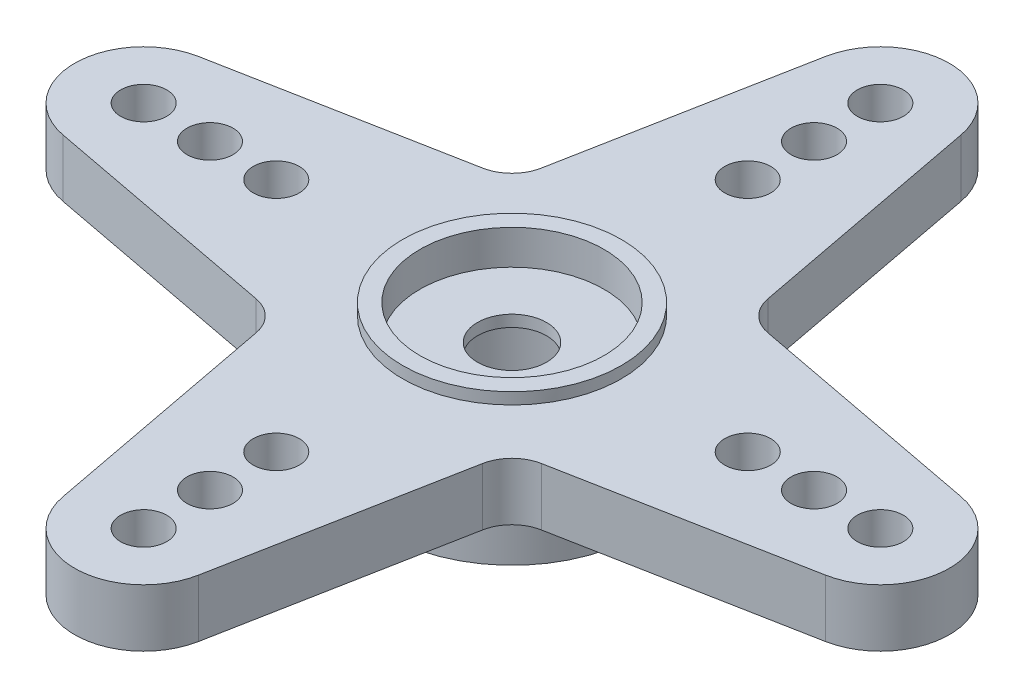
SolidWorks part; units mm, degrees
ref_plane "Front Plane" through (0, 0, 0) normal (0, 0, 1) x (1, 0, 0)
ref_plane "Top Plane" through (0, 0, 0) normal (0, 1, 0) x (1, 0, 0)
ref_plane "Right Plane" through (0, 0, 0) normal (1, 0, 0) x (0, 0, -1)
sketch "Sketch1" plane through (0, 0, 0) normal (0, 1, 0) x (1, 0, 0)
  line L0 (-1000, 0) -> (49000, 0) construction
  line L1 (0, -1000) -> (0, 49000) construction
  line L2 (-3.9044, 4.9148) -> (-2.3393, 13.1449)
  line L3 (3.9044, 4.9148) -> (2.3393, 13.1449)
  line L4 (4.9148, 3.9044) -> (13.1449, 2.3393)
  line L5 (4.9148, -3.9044) -> (13.1449, -2.3393)
  line L6 (3.9044, -4.9148) -> (2.3393, -13.1449)
  line L7 (-3.9044, -4.9148) -> (-2.3393, -13.1449)
  line L8 (-4.0659, 4.0659) -> (-4.0659, -4.0659) construction
  line L9 (-4.0659, 4.0659) -> (4.0659, 4.0659) construction
  line L10 (-4.0659, -4.0659) -> (4.0659, -4.0659) construction
  line L11 (4.0659, 4.0659) -> (4.0659, -4.0659) construction
  line L12 (-4.9148, -3.9044) -> (-13.1449, -2.3393)
  line L13 (-4.9148, 3.9044) -> (-13.1449, 2.3393)
  circle A0 centre (0, 0) radius 1.1906
  circle A1 centre (0, 0) radius 5.75 construction
  arc A2 (-2.3393, 13.1449) -> (2.3393, 13.1449) centre (0, 12.7) cw
  circle A3 centre (0, 12.7) radius 0.7937
  circle A4 centre (0, 10.414) radius 0.7937
  circle A5 centre (0, 8.128) radius 0.7937
  arc A6 (13.1449, 2.3393) -> (13.1449, -2.3393) centre (12.7, 0) cw
  circle A7 centre (12.7, 0) radius 0.7937
  circle A8 centre (10.414, 0) radius 0.7937
  circle A9 centre (8.128, 0) radius 0.7937
  arc A10 (2.3393, -13.1449) -> (-2.3393, -13.1449) centre (0, -12.7) cw
  circle A11 centre (0, -12.7) radius 0.7937
  circle A12 centre (0, -10.414) radius 0.7937
  circle A13 centre (0, -8.128) radius 0.7938
  arc A14 (-13.1449, -2.3393) -> (-13.1449, 2.3393) centre (-12.7, 0) cw
  circle A15 centre (-12.7, 0) radius 0.7937
  circle A16 centre (-10.414, 0) radius 0.7937
  circle A17 centre (-8.128, 0) radius 0.7937
  arc A18 (3.9044, 4.9148) -> (4.9148, 3.9044) centre (5.1521, 5.1521) ccw
  arc A19 (-3.9044, -4.9148) -> (-4.9148, -3.9044) centre (-5.1521, -5.1521) ccw
  arc A20 (-3.9044, 4.9148) -> (-4.9148, 3.9044) centre (-5.1521, 5.1521) cw
  arc A21 (3.9044, -4.9148) -> (4.9148, -3.9044) centre (5.1521, -5.1521) cw
  point P56 (4.0659, 0)
  point P57 (-4.0659, 0)
  dimension "D1" = 11.5
  dimension "D2" = 2.3813
  dimension "D3" = 2.3813
  dimension "D5" = 1.5875
  dimension "D8" = 1.27
  dimension "D9" = 1.27
  dimension "D10" = 1.27
  dimension "D11" = 1.27
  dimension "D4" = 12.7
  dimension "D6" = 3
  dimension "D7" = 4
extrude "Boss-Extrude1" add sketch "Sketch1" along normal blind 1.9844
sketch "Sketch2" plane through (0, 1.9844, 0) normal (0, 1, 0) x (1, 0, 0)
  circle A0 centre (0, 0) radius 3.175
  dimension "D1" = 6.35
extrude "Cut-Extrude1" cut sketch "Sketch2" against normal blind 0.7937
sketch "Sketch3" plane through (0, 0, 0) normal (0, -1, 0) x (1, 0, 0)
  circle A0 centre (0, 0) radius 4.3656
  dimension "D1" = 8.7312
extrude "Boss-Extrude2" add sketch "Sketch3" along normal blind 2.3813
sketch "Sketch4" plane through (0, -2.3813, 0) normal (0, -1, 0) x (1, 0, 0)
  circle A0 centre (0, 0) radius 2.7781
  dimension "D1" = 5.5562
extrude "Cut-Extrude2" cut sketch "Sketch4" against normal blind 3.175
sketch "Sketch5" plane through (0, 1.9844, 0) normal (0, 1, 0) x (1, 0, 0)
  circle A0 centre (0, 0) radius 3.175
  circle A1 centre (0, 0) radius 3.7703
  dimension "D1" = 7.5406
extrude "Boss-Extrude3" add sketch "Sketch5" along normal blind 0.3969
